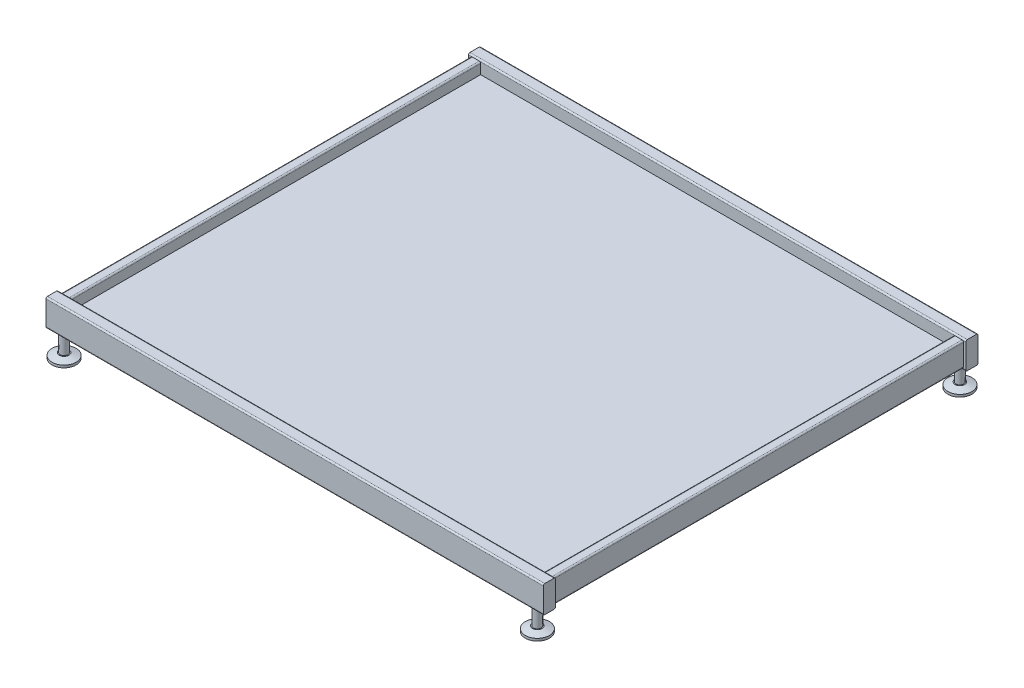
SolidWorks part; units mm, degrees
note: '?' marks a value the reader was unsure of.
material "AISI 304"
ref_plane "Спереди" through (0, 0, 0) normal (0, 0, 1) x (1, 0, 0)
ref_plane "Сверху" through (0, 0, 0) normal (0, 1, 0) x (1, 0, 0)
ref_plane "Справа" through (0, 0, 0) normal (1, 0, 0) x (0, 0, -1)
ref_axis "ОсьX" through (-88.99, 0, 0) along (1, 0, 0)?
ref_axis "ОсьZ" through (0, 55, 0) along (0, -1, 0)?
ref_axis "ОсьY" through (0, 0, -88.99) along (0, 0, 1)?
sketch "Эскиз1" plane through (0, 0, 0) normal (0, 0, 1) x (1, 0, 0)
  line L0 (0, 96.9354) -> (0, -116.3979) construction
  line L1 (-507, 25) -> (-493, 25)
  line L2 (-510, 22) -> (-510, -22)
  line L3 (-507, -25) -> (-493, -25)
  line L4 (-490, 22) -> (-490, -22)
  line L5 (-508.5, 22) -> (-508.5, -22)
  line L6 (-507, -23.5) -> (-493, -23.5)
  line L7 (-491.5, 22) -> (-491.5, -22)
  line L8 (-507, 23.5) -> (-493, 23.5)
  line L9 (507, 23.5) -> (493, 23.5)
  line L10 (491.5, 22) -> (491.5, -22)
  line L11 (507, -23.5) -> (493, -23.5)
  line L12 (508.5, 22) -> (508.5, -22)
  line L13 (490, 22) -> (490, -22)
  line L14 (507, -25) -> (493, -25)
  line L15 (510, 22) -> (510, -22)
  line L16 (507, 25) -> (493, 25)
  arc A0 (-510, -22) -> (-507, -25) centre (-507, -22) ccw
  arc A1 (-493, -25) -> (-490, -22) centre (-493, -22) ccw
  arc A2 (-493, 25) -> (-490, 22) centre (-493, 22) cw
  arc A3 (-507, 25) -> (-510, 22) centre (-507, 22) ccw
  arc A4 (-508.5, -22) -> (-507, -23.5) centre (-507, -22) ccw
  arc A5 (-493, -23.5) -> (-491.5, -22) centre (-493, -22) ccw
  arc A6 (-493, 23.5) -> (-491.5, 22) centre (-493, 22) cw
  arc A7 (-507, 23.5) -> (-508.5, 22) centre (-507, 22) ccw
  arc A8 (507, 23.5) -> (508.5, 22) centre (507, 22) cw
  arc A9 (493, 23.5) -> (491.5, 22) centre (493, 22) ccw
  arc A10 (493, -23.5) -> (491.5, -22) centre (493, -22) cw
  arc A11 (508.5, -22) -> (507, -23.5) centre (507, -22) cw
  arc A12 (507, 25) -> (510, 22) centre (507, 22) cw
  arc A13 (493, 25) -> (490, 22) centre (493, 22) ccw
  arc A14 (493, -25) -> (490, -22) centre (493, -22) cw
  arc A15 (510, -22) -> (507, -25) centre (507, -22) cw
  point P4 (-490, 0)
  point P8 (-500, 25)
  dimension "D4" = 3
  dimension "D1" = 20
  dimension "D2" = 50
  dimension "D3" = 1000
  dimension "D5" = 1.5
extrude "Бобышка-Вытянуть1" add sketch "Эскиз1" along normal mid plane 850
sketch "Эскиз2" plane through (0, 0, 0) normal (1, 0, 0) x (0, 0, -1)
  line L0 (425, -25) -> (425, 25)
  line L1 (428, 28) -> (447, 28)
  line L2 (450, 25) -> (450, -25)
  line L6 (425, -22) -> (425, 22) construction
  line L7 (-425, -25) -> (425, -25) construction
  line L8 (-425, 25) -> (425, 25) construction
  line L9 (0, 70.6695) -> (0, -66.6142) construction
  line L16 (425, 0) -> (409.8907, 0) construction
  line L17 (428, -28) -> (447, -28)
  line L18 (-428, -28) -> (-447, -28)
  line L19 (-450, 25) -> (-450, -25)
  line L20 (-428, 28) -> (-447, 28)
  line L21 (-425, -25) -> (-425, 25)
  arc A3 (447, 28) -> (450, 25) centre (447, 25) cw
  arc A4 (425, 25) -> (428, 28) centre (428, 25) cw
  arc A10 (447, -28) -> (450, -25) centre (447, -25) ccw
  arc A11 (425, -25) -> (428, -28) centre (428, -25) ccw
  arc A12 (-425, -25) -> (-428, -28) centre (-428, -25) cw
  arc A13 (-447, -28) -> (-450, -25) centre (-447, -25) cw
  arc A14 (-425, 25) -> (-428, 28) centre (-428, 25) ccw
  arc A15 (-447, 28) -> (-450, 25) centre (-447, 25) ccw
  point P29 (425, 28)
  dimension "D1" = 3
  dimension "D2" = 25
extrude "Бобышка-Вытянуть4" add sketch "Эскиз2" along normal offset from surface 5 and the other way offset from surface (515 mm away) 5 up to face at (510, 0, 0) offset beyond the face yes other way up to face at (-510, 0, 0)
sketch "Эскиз3" plane through (0, 0, 0) normal (0, 1, 0) x (1, 0, 0)
  line L1 (-490, 425) -> (490, 425)
  line L2 (-490, 425) -> (-490, -425)
  line L3 (-490, -425) -> (490, -425)
  line L4 (490, 425) -> (490, -425)
  line L6 (490, -425) -> (490, 425) construction
  line L7 (-490, -425) -> (-490, 425) construction
  line L8 (493, -425) -> (-515, -425) construction
extrude "Бобышка-Вытянуть5" add sketch "Эскиз3" along normal blind 2
sketch "Эскиз4" plane through (-490, 0, 0) normal (1, 0, 0) x (0, 0, -1)
  line L0 (-437.5, 28) -> (-437.5, -139.1956) construction
  line L1 (-447, 28) -> (-428, 28) construction
  line L2 (-437.5, -28) -> (-429.5, -28)
  line L3 (-428, -28) -> (-447, -28) construction
  line L4 (-429.5, -28) -> (-429.5, -65)
  line L5 (-429.5, -65) -> (-427.5, -65)
  line L6 (-427.5, -65) -> (-412.5, -70)
  line L7 (-412.5, -70) -> (-412.5, -75)
  line L8 (-412.5, -75) -> (-437.5, -75)
  line L9 (-437.5, -75) -> (-437.5, -28)
  line L10 (-425, -25) -> (425, -25) construction
  point P5 (-437.5, 28)
  dimension "D1" = 50
  dimension "D2" = 16
  dimension "D3" = 5
  dimension "D4" = 10
  dimension "D5" = 50
  dimension "D6" = 2
revolve "Повернуть1" add sketch "Эскиз4" angle 360 mid plane about L0
mirror "Зеркальное отражение1" about plane through (0, 0, 0) normal (1, 0, 0) of "Повернуть1"
mirror "Зеркальное отражение2" about plane through (0, 0, 0) normal (0, 0, 1) of "Зеркальное отражение1", "Повернуть1"
